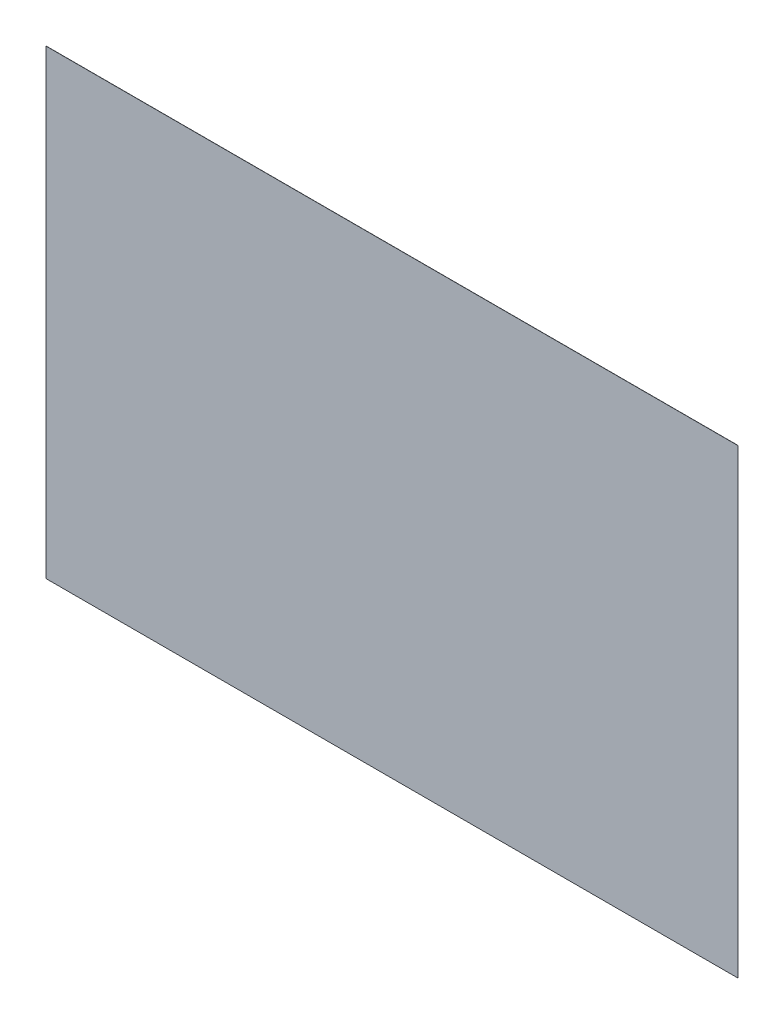
SolidWorks part; units mm, degrees
ref_plane "Спереди" through (0, 0, 0) normal (0, 0, 1) x (1, 0, 0)
ref_plane "Сверху" through (0, 0, 0) normal (0, 1, 0) x (1, 0, 0)
ref_plane "Справа" through (0, 0, 0) normal (1, 0, 0) x (0, 0, -1)
sketch "Эскиз1" plane through (0, 0, 0) normal (0, 0, 1) x (1, 0, 0)
  line L1 (-1942.5, 1295) -> (1942.5, 1295)
  line L2 (-1942.5, 1295) -> (-1942.5, -1295)
  line L3 (-1942.5, -1295) -> (1942.5, -1295)
  line L4 (1942.5, 1295) -> (1942.5, -1295)
  line L5 (-1942.5, 1295) -> (1942.5, -1295) construction
  line L6 (-1942.5, -1295) -> (1942.5, 1295) construction
  point P1 (0, 0)
extrude "Бобышка-Вытянуть1" add sketch "Эскиз1" along normal blind 1 contours L2 L1 L4 L3
